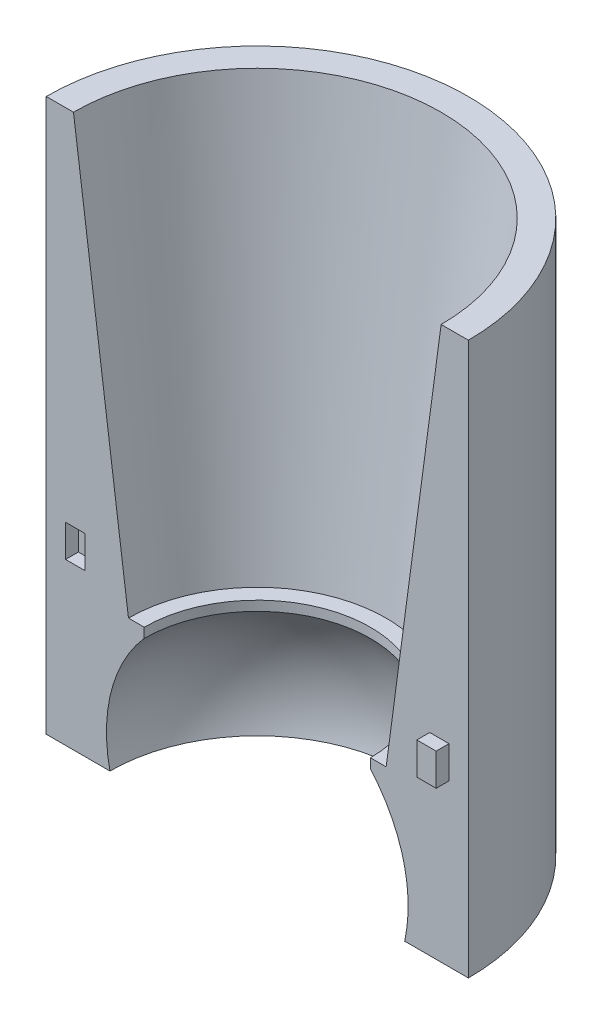
SolidWorks part; units mm, degrees
ref_plane "Front Plane" through (0, 0, 0) normal (0, 0, 1) x (1, 0, 0)
ref_plane "Top Plane" through (0, 0, 0) normal (0, 1, 0) x (1, 0, 0)
ref_plane "Right Plane" through (0, 0, 0) normal (1, 0, 0) x (0, 0, -1)
sketch "Sketch3" plane through (0, 0, 0) normal (0, 0, 1) x (1, 0, 0)
  line L0 (4.5628, -59.7537) -> (-20.4372, -59.7537)
  line L1 (41.8909, -71.9367) -> (16.8909, -71.9367)
  line L2 (-9.1279, 14.6155) -> (-9.1279, -32.2145)
  line L4 (-9.1279, -13.7995) -> (-41.8909, -13.7995)
  line L5 (-9.1279, -13.7995) -> (-9.1279, 71.9367)
  line L6 (-9.1279, 71.9367) -> (-41.8909, 71.9367)
  line L7 (-41.8909, -13.7995) -> (-41.8909, 71.9367)
  line L8 (-26.6804, 8.2005) -> (-9.1279, 8.2005)
  line L9 (-26.6804, 8.2005) -> (-26.6804, 6.6979)
  line L10 (-9.1279, 95.8585) -> (-9.1279, -91.8555) construction
  line L11 (-26.6804, 8.2005) -> (-29.1283, 8.2005)
  line L12 (-29.1283, 8.2005) -> (-37.6602, 71.9367)
  arc A0 (-9.1279, 14.6155) -> (-9.1279, -32.2145) centre (-9.1279, -8.7995) ccw
  dimension "D1" = 46.83
  dimension "D2" = 5
  dimension "D3" = 32.7631
  dimension "D4" = 17
revolve "Revolve8" add sketch "Sketch3" angle 180 about L10 region at (-36.941, 23.3904, 0)
sketch "Sketch5" plane through (0, 0, 0) normal (0, 0, 1) x (1, 0, 0)
  line L0 (23.6352, -13.7995) -> (23.6352, 71.9367) construction
  line L1 (17.6352, 16.2005) -> (20.6352, 16.2005)
  line L2 (17.6352, 16.2005) -> (17.6352, 11.2005)
  line L3 (17.6352, 11.2005) -> (20.6352, 11.2005)
  line L4 (20.6352, 16.2005) -> (20.6352, 11.2005)
  line L5 (13.747, -13.7995) -> (23.6352, -13.7995) construction
  dimension "D1" = 3
  dimension "D2" = 25
  dimension "D3" = 5
  dimension "D4" = 3
extrude "Boss-Extrude1" add sketch "Sketch5" along normal blind 2
sketch "Sketch6" plane through (0, 0, 0) normal (0, 0, 1) x (1, 0, 0)
  line L0 (-32.0028, -13.7995) -> (-41.8909, -13.7995) construction
  line L1 (-38.8909, 16.2005) -> (-35.8909, 16.2005)
  line L2 (-38.8909, 16.2005) -> (-38.8909, 11.2005)
  line L3 (-38.8909, 11.2005) -> (-35.8909, 11.2005)
  line L4 (-35.8909, 16.2005) -> (-35.8909, 11.2005)
  line L5 (-41.8909, -13.7995) -> (-41.8909, 71.9367) construction
  dimension "D1" = 25
  dimension "D2" = 5
  dimension "D3" = 3
  dimension "D4" = 3
extrude "Cut-Extrude1" cut sketch "Sketch6" against normal blind 2
